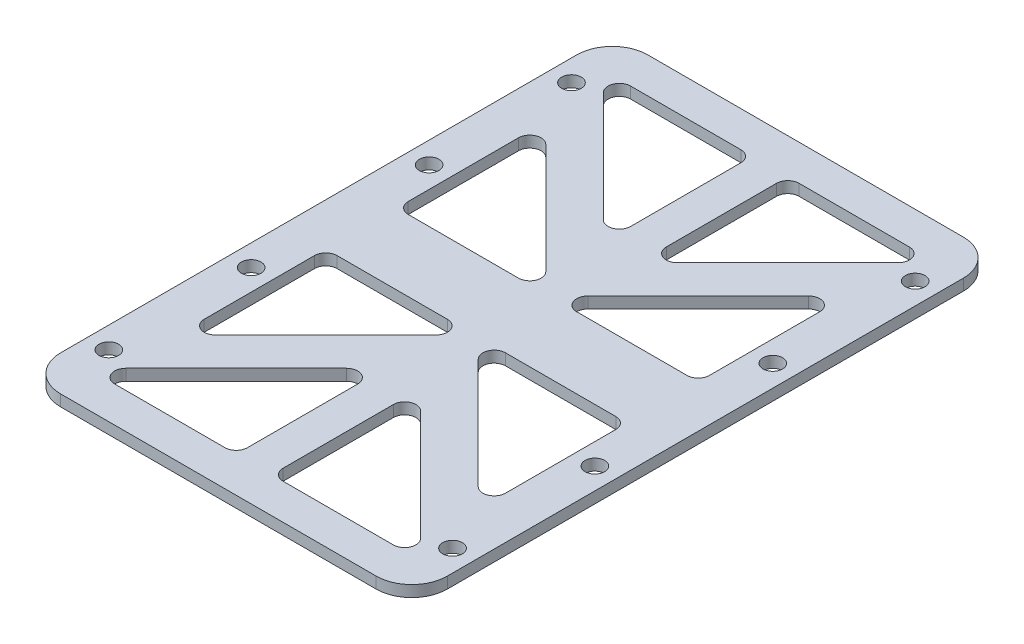
SolidWorks part; units mm, degrees
material "Carbon Fiber, Plain Weave"
ref_plane "Front Plane" through (0, 0, 0) normal (0, 0, 1) x (1, 0, 0)
ref_plane "Top Plane" through (0, 0, 0) normal (0, 1, 0) x (1, 0, 0)
ref_plane "Right Plane" through (0, 0, 0) normal (1, 0, 0) x (0, 0, -1)
ref_axis "Axis1" through (0, 0, -88.99) along (0, 0, 1)
ref_axis "Axis2" through (0, -55, 0) along (0, 1, 0)
ref_axis "Axis3" through (-88.99, 0, 0) along (1, 0, 0)
sketch "Sketch1" plane through (0, 0, 0) normal (0, 1, 0) x (1, 0, 0)
  line L1 (-44.329, -82.5) -> (44.329, -82.5)
  line L2 (-54.329, -72.5) -> (-54.329, 72.5)
  line L3 (-44.329, 82.5) -> (44.329, 82.5)
  line L4 (54.329, -72.5) -> (54.329, 72.5)
  line L5 (-54.329, -82.5) -> (54.329, 82.5) construction
  line L6 (-54.329, 82.5) -> (54.329, -82.5) construction
  arc A0 (44.329, 82.5) -> (54.329, 72.5) centre (44.329, 72.5) cw
  arc A1 (44.329, -82.5) -> (54.329, -72.5) centre (44.329, -72.5) ccw
  arc A2 (-44.329, -82.5) -> (-54.329, -72.5) centre (-44.329, -72.5) cw
  arc A3 (-54.329, 72.5) -> (-44.329, 82.5) centre (-44.329, 72.5) cw
  point P0 (0, 0)
  dimension "D3" = 10
  dimension "D1" = 54.329
  dimension "D2" = 165
extrude "Boss-Extrude1" add sketch "Sketch1" along normal blind 3.175
hole_wizard "M5 Clearance Hole1" positions "Sketch3" profile "Sketch2" hole size "M5" standard "ANSI Metric" end condition through all
sketch "Sketch3" plane through (0, 3.175, 0) normal (0, 1, 0) x (1, 0, 0)
  line L2 (-48.29, 0) -> (0, 0) construction
  line L4 (-48.29, 65) -> (-48.29, -65) construction
  line L6 (0, 0) -> (0, 25) construction
  point P0 (-48.29, 65)
  point P18 (-48.29, -65)
  point P27 (48.29, -65)
  point P29 (48.29, 65)
  point P40 (-48.29, 25)
  point P45 (-48.29, -25)
  point P47 (48.29, 25)
  point P48 (48.29, -25)
  dimension "D1" = 130
  dimension "D2" = 96.58
  dimension "D3" = 50
sketch "Sketch2" plane through (-48.29, 3.175, -65) normal (1, 0, 0) x (0, 0, 1)
  line L0 (0, 0) -> (0, 3.175)
  line L1 (0, 3.175) -> (2.75, 3.175)
  line L2 (2.75, 3.175) -> (2.75, 0)
  line L5 (2.75, 0) -> (0, 0)
  line L11 (0, -6.35) -> (0, 107.95) construction
  dimension "Thru Hole Dia." = 5.5
  dimension "Thru Hole Depth" = 3.175
sketch "Sketch4" plane through (0, 3.175, 0) normal (0, 1, 0) x (1, 0, 0)
  line L0 (-42.329, 44.154) -> (-42.329, 13.175)
  line L1 (-39.154, 10) -> (-8.175, 10)
  line L2 (-5.9299, 15.4201) -> (-36.9089, 46.3991)
  line L5 (-54.329, 72.5) -> (-54.329, -72.5) construction
  line L6 (39.154, 72.5) -> (8.175, 72.5)
  line L7 (0, 0) -> (0, 16.2845) construction
  line L8 (-5, 69.325) -> (-5, 38.346)
  line L9 (-10.4201, 36.1009) -> (-41.3991, 67.0799)
  line L10 (-39.154, 72.5) -> (-8.175, 72.5)
  line L11 (10.4201, 36.1009) -> (41.3991, 67.0799)
  line L12 (5, 69.325) -> (5, 38.346)
  line L13 (5.9299, 15.4201) -> (36.9089, 46.3991)
  line L14 (39.154, 10) -> (8.175, 10)
  line L15 (42.329, 44.154) -> (42.329, 13.175)
  line L16 (0, 0) -> (54.329, 0) construction
  line L17 (54.329, -72.5) -> (54.329, 72.5) construction
  line L18 (42.329, -44.154) -> (42.329, -13.175)
  line L19 (39.154, -10) -> (8.175, -10)
  line L20 (5.9299, -15.4201) -> (36.9089, -46.3991)
  line L21 (5, -69.325) -> (5, -38.346)
  line L22 (10.4201, -36.1009) -> (41.3991, -67.0799)
  line L23 (-39.154, -72.5) -> (-8.175, -72.5)
  line L24 (-10.4201, -36.1009) -> (-41.3991, -67.0799)
  line L25 (-5, -69.325) -> (-5, -38.346)
  line L26 (39.154, -72.5) -> (8.175, -72.5)
  line L27 (-5.9299, -15.4201) -> (-36.9089, -46.3991)
  line L28 (-39.154, -10) -> (-8.175, -10)
  line L29 (-42.329, -44.154) -> (-42.329, -13.175)
  line L30 (23.6645, 72.5) -> (23.6645, 92.5) construction
  line L31 (23.6645, 10) -> (23.6645, -10) construction
  line L32 (44.329, 82.5) -> (-44.329, 82.5) construction
  arc A0 (-42.329, 13.175) -> (-39.154, 10) centre (-39.154, 13.175) ccw
  arc A1 (-8.175, 10) -> (-5.9299, 15.4201) centre (-8.175, 13.175) ccw
  arc A2 (-36.9089, 46.3991) -> (-42.329, 44.154) centre (-39.154, 44.154) ccw
  arc A3 (-5, 38.346) -> (-10.4201, 36.1009) centre (-8.175, 38.346) cw
  arc A4 (-41.3991, 67.0799) -> (-39.154, 72.5) centre (-39.154, 69.325) cw
  arc A5 (-8.175, 72.5) -> (-5, 69.325) centre (-8.175, 69.325) cw
  arc A6 (8.175, 72.5) -> (5, 69.325) centre (8.175, 69.325) ccw
  arc A7 (41.3991, 67.0799) -> (39.154, 72.5) centre (39.154, 69.325) ccw
  arc A8 (5, 38.346) -> (10.4201, 36.1009) centre (8.175, 38.346) ccw
  arc A9 (36.9089, 46.3991) -> (42.329, 44.154) centre (39.154, 44.154) cw
  arc A10 (8.175, 10) -> (5.9299, 15.4201) centre (8.175, 13.175) cw
  arc A11 (42.329, 13.175) -> (39.154, 10) centre (39.154, 13.175) cw
  arc A12 (42.329, -13.175) -> (39.154, -10) centre (39.154, -13.175) ccw
  arc A13 (8.175, -10) -> (5.9299, -15.4201) centre (8.175, -13.175) ccw
  arc A14 (36.9089, -46.3991) -> (42.329, -44.154) centre (39.154, -44.154) ccw
  arc A15 (5, -38.346) -> (10.4201, -36.1009) centre (8.175, -38.346) cw
  arc A16 (41.3991, -67.0799) -> (39.154, -72.5) centre (39.154, -69.325) cw
  arc A17 (8.175, -72.5) -> (5, -69.325) centre (8.175, -69.325) cw
  arc A18 (-8.175, -72.5) -> (-5, -69.325) centre (-8.175, -69.325) ccw
  arc A19 (-41.3991, -67.0799) -> (-39.154, -72.5) centre (-39.154, -69.325) ccw
  arc A20 (-5, -38.346) -> (-10.4201, -36.1009) centre (-8.175, -38.346) ccw
  arc A21 (-36.9089, -46.3991) -> (-42.329, -44.154) centre (-39.154, -44.154) cw
  arc A22 (-8.175, -10) -> (-5.9299, -15.4201) centre (-8.175, -13.175) cw
  arc A23 (-42.329, -13.175) -> (-39.154, -10) centre (-39.154, -13.175) cw
  point P84 (23.6645, 0)
  point P85 (23.6645, 82.5)
  dimension "D1" = 10
  dimension "D3" = 3.175
  dimension "D2" = 12
  dimension "D4" = 45
  dimension "D5" = 20
extrude "Cut-Extrude1" cut sketch "Sketch4" against normal through all
sketch "Sketch5" plane through (0, 3.175, 0) normal (0, 1, 0) x (1, 0, 0)
  line L0 (-52.5367, 78.2126) -> (-43.5846, 91.0749)
  line L1 (-40, 102.5) -> (-40, 187.5)
  line L2 (-30, 197.5) -> (30, 197.5)
  line L3 (-52.5367, -78.2126) -> (-43.5846, -91.0749)
  line L4 (-40, -102.5) -> (-40, -190)
  line L5 (0, 0) -> (0, 197.5) construction
  line L6 (52.5367, 78.2126) -> (43.5846, 91.0749)
  line L7 (40, 102.5) -> (40, 187.5)
  line L8 (-60, -210) -> (-65, -210)
  line L9 (-75, -220) -> (-75, -240)
  line L10 (44.329, 82.5) -> (-44.329, 82.5)
  line L11 (-54.329, 72.5) -> (-54.329, -72.5)
  line L12 (-44.329, -82.5) -> (44.329, -82.5)
  line L13 (54.329, -72.5) -> (54.329, 72.5)
  line L14 (44.329, 82.5) -> (-44.329, 82.5)
  line L15 (-54.329, 72.5) -> (-54.329, -72.5)
  line L16 (-44.329, -82.5) -> (44.329, -82.5)
  line L17 (54.329, -72.5) -> (54.329, 72.5)
  line L18 (-65, -250) -> (65, -250)
  line L19 (0, 0) -> (0, -250) construction
  line L20 (75, -220) -> (75, -240)
  line L21 (60, -210) -> (65, -210)
  line L22 (40, -102.5) -> (40, -190)
  line L23 (52.5367, -78.2126) -> (43.5846, -91.0749)
  arc A0 (-44.329, 82.5) -> (-54.329, 72.5) centre (-44.329, 72.5) ccw construction
  arc A1 (-43.5846, 91.0749) -> (-40, 102.5) centre (-60, 102.5) ccw
  arc A2 (-40, 187.5) -> (-30, 197.5) centre (-30, 187.5) cw
  arc A3 (40, 187.5) -> (30, 197.5) centre (30, 187.5) ccw
  arc A4 (-43.5846, -91.0749) -> (-40, -102.5) centre (-60, -102.5) cw
  arc A5 (54.329, 72.5) -> (44.329, 82.5) centre (44.329, 72.5) ccw
  arc A6 (-44.329, 82.5) -> (-54.329, 72.5) centre (-44.329, 72.5) ccw
  arc A7 (-54.329, -72.5) -> (-44.329, -82.5) centre (-44.329, -72.5) ccw
  arc A8 (44.329, -82.5) -> (54.329, -72.5) centre (44.329, -72.5) ccw
  arc A9 (54.329, 72.5) -> (44.329, 82.5) centre (44.329, 72.5) ccw
  arc A10 (-44.329, 82.5) -> (-54.329, 72.5) centre (-44.329, 72.5) ccw
  arc A11 (-54.329, -72.5) -> (-44.329, -82.5) centre (-44.329, -72.5) ccw
  arc A12 (44.329, -82.5) -> (54.329, -72.5) centre (44.329, -72.5) ccw
  arc A13 (43.5846, 91.0749) -> (40, 102.5) centre (60, 102.5) cw
  arc A14 (-40, -190) -> (-60, -210) centre (-60, -190) cw
  arc A15 (-65, -210) -> (-75, -220) centre (-65, -220) ccw
  arc A16 (-75, -240) -> (-65, -250) centre (-65, -240) ccw
  arc A17 (75, -240) -> (65, -250) centre (65, -240) cw
  arc A18 (65, -210) -> (75, -220) centre (65, -220) cw
  arc A19 (40, -190) -> (60, -210) centre (60, -190) ccw
  arc A20 (43.5846, -91.0749) -> (40, -102.5) centre (60, -102.5) ccw
  dimension "D2" = 20
  dimension "D3" = 115
  dimension "D6" = 10
  dimension "D11" = 10
  dimension "D4" = 80
  dimension "D5" = 20
  dimension "D7" = 80
  dimension "D8" = 20
  dimension "D9" = 150
  dimension "D10" = 40
  dimension "D12" = 250
  dimension "D1" = 0
extrude "Boss-Extrude2" [suppressed] add sketch "Sketch5" against normal up to surface (0.762 mm away)
